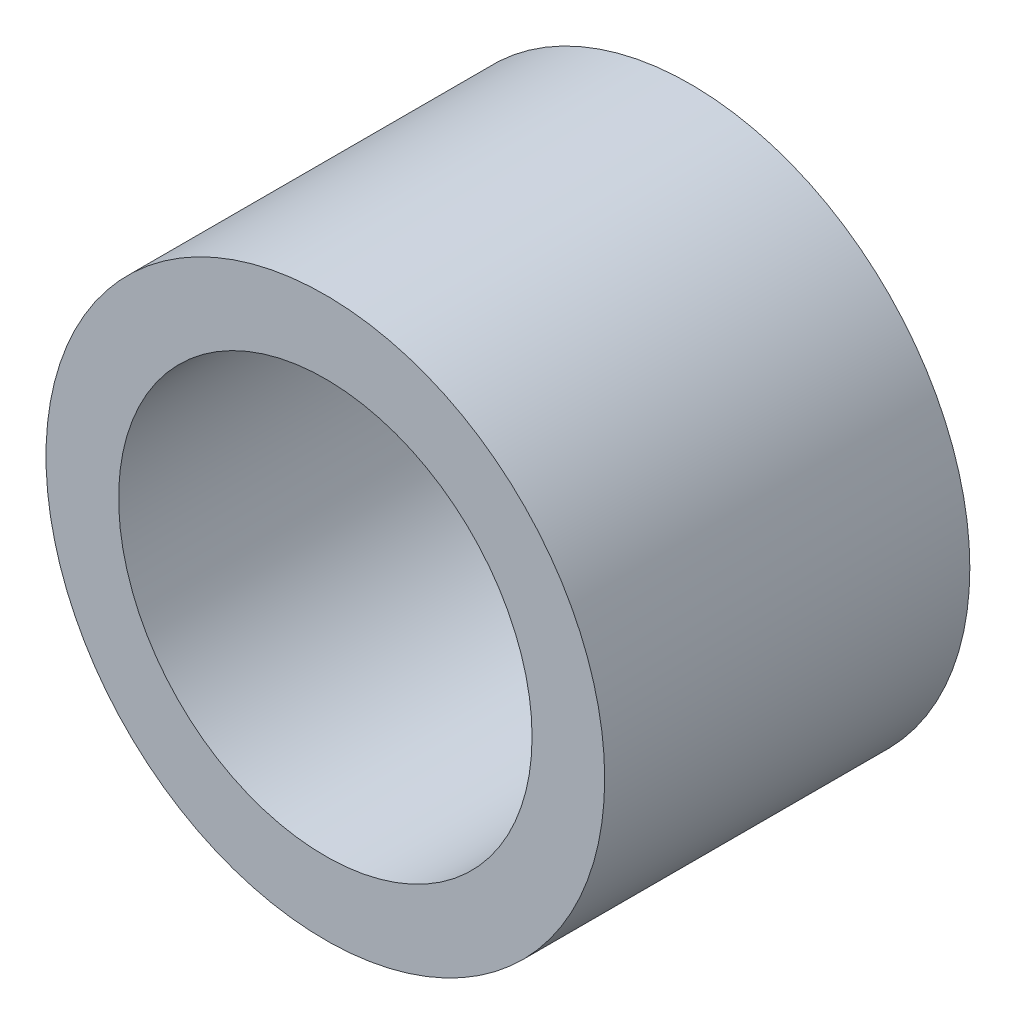
SolidWorks part; units mm, degrees
ref_plane "Front Plane" through (0, 0, 0) normal (0, 0, 1) x (1, 0, 0)
ref_plane "Top Plane" through (0, 0, 0) normal (0, 1, 0) x (1, 0, 0)
ref_plane "Right Plane" through (0, 0, 0) normal (1, 0, 0) x (0, 0, -1)
sketch "Sketch1" plane through (0, 0, 0) normal (0, 0, 1) x (1, 0, 0)
  circle A0 centre (0, 0) radius 4.699
  circle A1 centre (0, 0) radius 6.35
  dimension "D1" = 12.7
  dimension "D2" = 9.398
extrude "Boss-Extrude1" add sketch "Sketch1" along normal up to surface (8.3 mm away)
